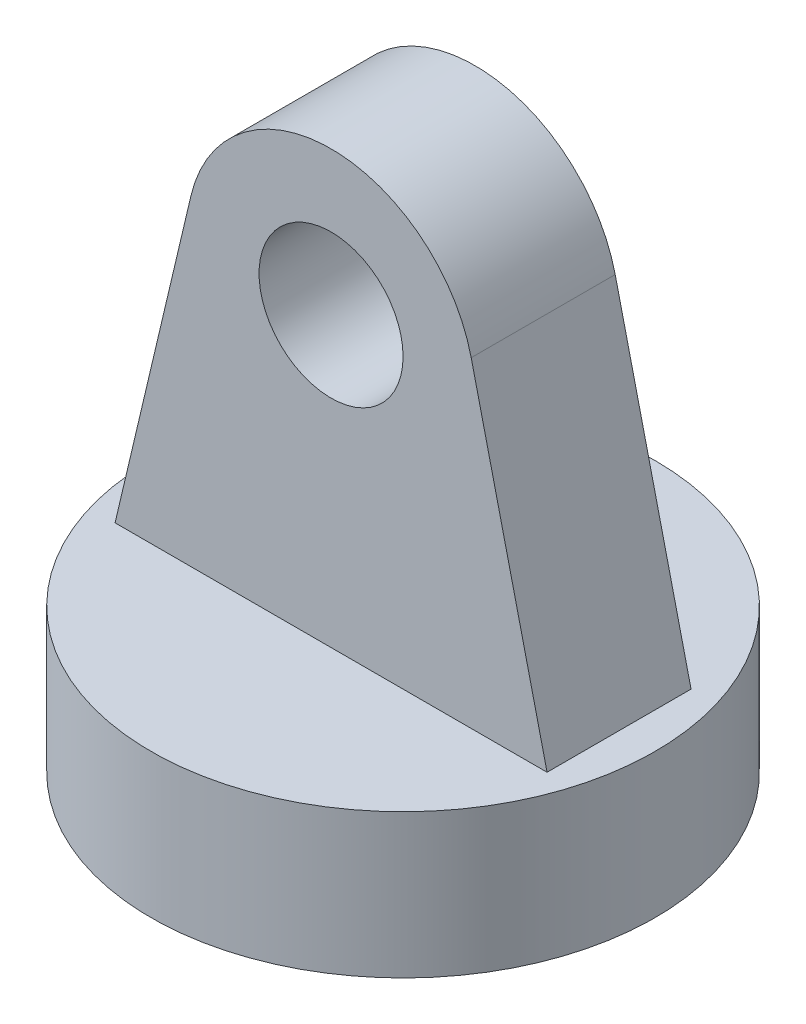
SolidWorks part; units mm, degrees
ref_plane "前视基准面" through (0, 0, 0) normal (0, 0, 1) x (1, 0, 0)
ref_plane "上视基准面" through (0, 0, 0) normal (0, 1, 0) x (1, 0, 0)
ref_plane "右视基准面" through (0, 0, 0) normal (1, 0, 0) x (0, 0, -1)
other "Configuration Table"
sketch "草图1" plane through (0, 0, 0) normal (0, 0, 1) x (1, 0, 0)
  line L0 (-10.5374, 285.1641) -> (-5.2695, 307.4632)
  line L1 (-10.5374, 285.1641) -> (19.4626, 285.1641) construction
  line L2 (19.4626, 285.1641) -> (14.1947, 307.4632)
  line L3 (4.4626, 305.1641) -> (4.4626, 285.1641) construction
  line L4 (-10.5374, 285.1641) -> (-10.5374, 280.1641)
  line L5 (-10.5374, 280.1641) -> (19.4626, 280.1641)
  line L6 (19.4626, 280.1641) -> (19.4626, 285.1641)
  circle A0 centre (4.4626, 305.1641) radius 5
  circle A1 centre (4.4626, 305.1641) radius 10
  dimension "D1" = 10
  dimension "D2" = 20
  dimension "D3" = 20
  dimension "D4" = 30
  dimension "D5" = 5
extrude "凸台-拉伸1" add sketch "草图1" along normal blind 10 contours A1 A0 | A1 L0 L4 L5 L6 L2 region at (4.4626, 288.9706, 0) region at (4.4626, 314.8812, 0)
sketch "草图2" plane through (0, 280.1641, 0) normal (0, -1, 0) x (1, 0, 0)
  line L0 (4.4626, 10) -> (4.4626, 0) construction
  line L1 (-10.5374, 10) -> (19.4626, 10) construction
  line L2 (-10.5374, 0) -> (19.4626, 0) construction
  circle A0 centre (4.4626, 5) radius 17.5
  dimension "D1" = 35
extrude "凸台-拉伸2" add sketch "草图2" against normal blind 5 and the other way blind 5
